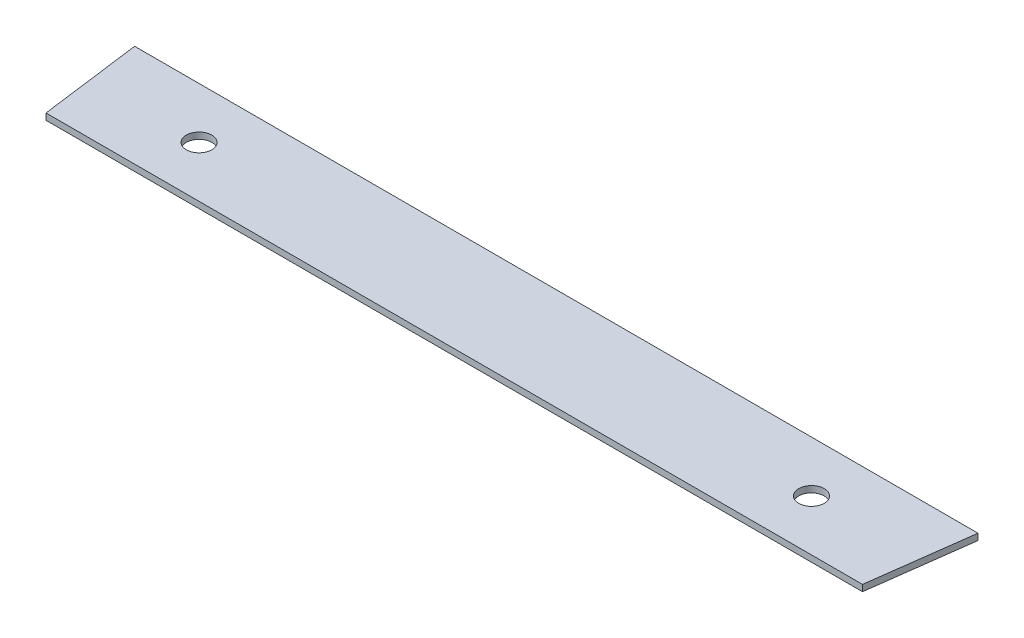
SolidWorks part; units mm, degrees
ref_plane "Front Plane" through (0, 0, 0) normal (0, 0, 1) x (1, 0, 0)
ref_plane "Top Plane" through (0, 0, 0) normal (0, 1, 0) x (1, 0, 0)
ref_plane "Right Plane" through (0, 0, 0) normal (1, 0, 0) x (0, 0, -1)
sketch "Sketch1" plane through (0, 0, 0) normal (0, 1, 0) x (1, 0, 0)
  line L0 (-203.2, 0) -> (203.2, 0) construction
  line L1 (203.2, -25.4) -> (-203.2, -25.4)
  line L2 (203.2, -25.4) -> (203.2, 25.4)
  line L3 (203.2, 25.4) -> (-203.2, 25.4)
  line L4 (-203.2, -25.4) -> (-203.2, 25.4)
  line L5 (203.2, -25.4) -> (-203.2, 25.4) construction
  line L6 (203.2, 25.4) -> (-203.2, -25.4) construction
  line L7 (-203.2, -25.4) -> (-209.8879, 25.4)
  line L8 (-209.8879, 25.4) -> (-203.2, 25.4)
  line L9 (203.2, -25.4) -> (209.8879, 25.4)
  line L10 (209.8879, 25.4) -> (203.2, 25.4)
  circle A0 centre (-152.4, 0) radius 6.35
  circle A1 centre (152.4, 0) radius 6.35
  point P0 (0, 0)
  dimension "D1" = 406.4
  dimension "D5" = 12.7
  dimension "D2" = 50.8
  dimension "D3" = 304.8
  dimension "D4" = 152.4
  dimension "D6" = 7.5
  dimension "D7" = 7.5
extrude "Boss-Extrude1" add sketch "Sketch1" along normal blind 3.175 contours L4 L1 L2 L3 A1 A0 | L8 L7 L4 | L9 L10 L2 region at (0, 0, 0) region at (205.4293, 0, -8.4667) region at (-205.4293, 0, -8.4667)
